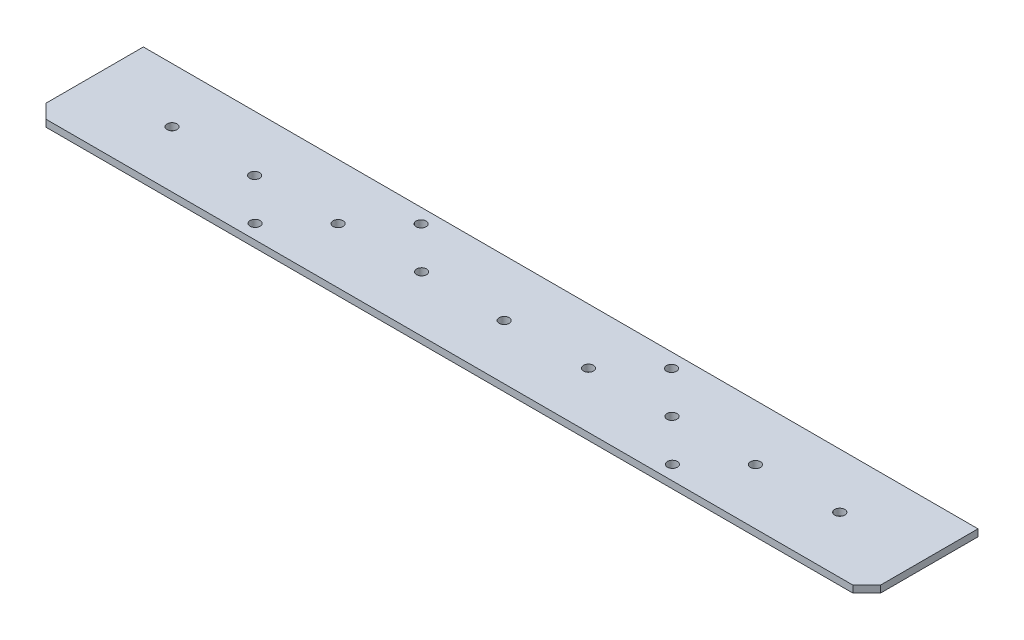
SolidWorks part; units mm, degrees
ref_plane "Front Plane" through (0, 0, 0) normal (0, 0, 1) x (1, 0, 0)
ref_plane "Top Plane" through (0, 0, 0) normal (0, 1, 0) x (1, 0, 0)
ref_plane "Right Plane" through (0, 0, 0) normal (1, 0, 0) x (0, 0, -1)
sketch "Sketch2" plane through (0, 0, 0) normal (0, 1, 0) x (1, 0, 0)
  line L0 (0, 0) -> (0, 50.8)
  line L1 (0, 50.8) -> (381, 50.8)
  line L2 (381, 50.8) -> (381, 0)
  line L3 (381, 0) -> (0, 0)
  dimension "D1" = 50.8
  dimension "D2" = 381
extrude "Boss-Extrude1" add sketch "Sketch2" along normal blind 3.175
sketch "Sketch3" plane through (0, 3.175, 0) normal (0, 1, 0) x (1, 0, 0)
  line L0 (190.5, 0) -> (190.5, 50.8) construction
  line L1 (0, 0) -> (381, 0) construction
  line L2 (381, 50.8) -> (0, 50.8) construction
  line L3 (38.1, 25.7969) -> (190.5, 25.0031) construction
  line L4 (342.9, 25.7969) -> (190.5, 25.0031) construction
  line L5 (0, 6.35) -> (6.35, 0)
  line L6 (6.35, 0) -> (0, 0)
  line L7 (0, 0) -> (0, 6.35)
  line L8 (374.65, 0) -> (381, 0)
  line L9 (381, 6.35) -> (374.65, 0)
  line L10 (381, 0) -> (381, 6.35)
  line L11 (247.65, 44.2526) -> (285.75, 6.5474) construction
  circle A0 centre (190.5, 25.0031) radius 2.286
  circle A1 centre (38.1, 25.7969) radius 2.286
  circle A2 centre (114.3, 25.4) radius 2.286
  circle A3 centre (76.2, 25.4) radius 2.286
  circle A4 centre (152.4, 25.4) radius 2.286
  circle A5 centre (228.6, 25.4) radius 2.286
  circle A6 centre (304.8, 25.4) radius 2.286
  circle A7 centre (266.7, 25.4) radius 2.286
  circle A8 centre (342.9, 25.7969) radius 2.286
  circle A9 centre (247.65, 44.2526) radius 2.286
  circle A10 centre (285.75, 6.5474) radius 2.286
  circle A11 centre (95.25, 6.5474) radius 2.286
  circle A12 centre (133.35, 44.2526) radius 2.286
  point P33 (0, 0)
  point P37 (266.7, 25.4)
  point P38 (0, 0)
  point P42 (0, 0)
  point P43 (0, 0)
  point P44 (0, 0)
  point P45 (0, 0)
  point P46 (0, 0)
  point P47 (0, 0)
  dimension "D1" = 4.572
  dimension "D2" = 0.7937
  dimension "D6" = 25.4
  dimension "D3" = 152.4
  dimension "D4" = 38.1
  dimension "D5" = 38.1
  dimension "D7" = 6.35
  dimension "D8" = 6.35
  dimension "D9" = 45
  dimension "D10" = 19.05
extrude "Cut-Extrude1" cut sketch "Sketch3" against normal up to next
